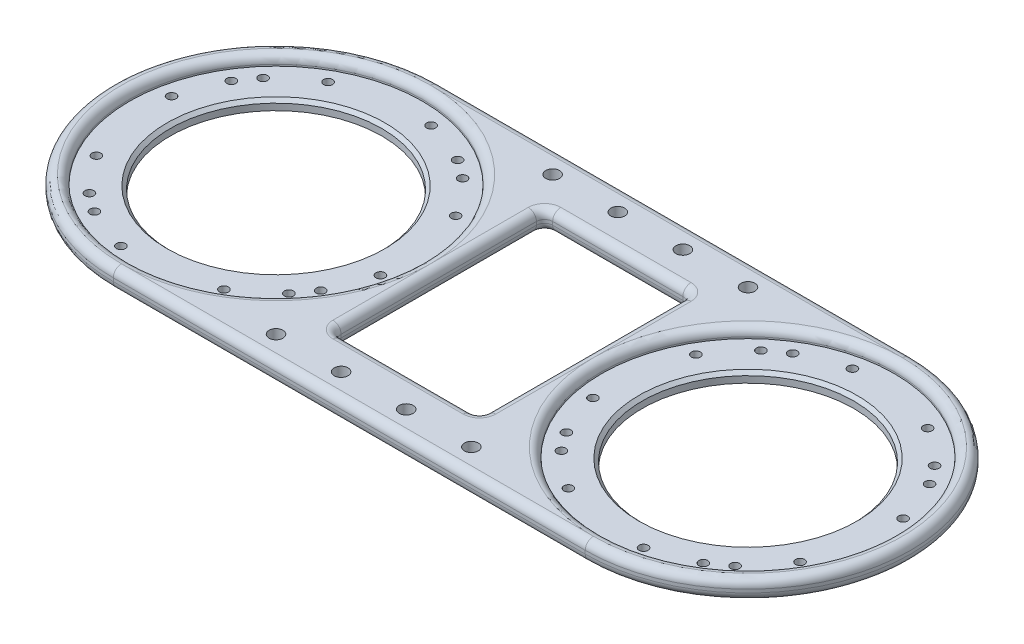
SolidWorks part; units mm, degrees
ref_plane "前视基准面" through (0, 0, 0) normal (0, 0, 1) x (1, 0, 0)
ref_plane "上视基准面" through (0, 0, 0) normal (0, 1, 0) x (1, 0, 0)
ref_plane "右视基准面" through (0, 0, 0) normal (1, 0, 0) x (0, 0, -1)
other "Configuration Table"
sketch "草图1" plane through (0, 0, 0) normal (0, 1, 0) x (1, 0, 0)
  line L0 (-145, 0) -> (145, 0) construction
  line L1 (-145, 100) -> (145, 100)
  line L2 (-145, -100) -> (145, -100)
  arc A0 (-145, 100) -> (-145, -100) centre (-145, 0) ccw
  arc A1 (145, -100) -> (145, 100) centre (145, 0) ccw
  point P3 (0, 0)
  dimension "D1" = 100
  dimension "D2" = 290
extrude "凸台-拉伸1" add sketch "草图1" along normal blind 6 and the other way blind 6
sketch "草图2" plane through (0, 0, 0) normal (0, 0, 1) x (1, 0, 0)
  line L0 (-145, 6) -> (-145, -6) construction
  line L1 (-145, -6) -> (-80, -6)
  line L2 (-145, -6) -> (145, -6) construction
  line L3 (-80, -6) -> (-80, 0)
  line L4 (-80, 0) -> (-55, 0)
  line L5 (-55, 0) -> (-55, 6)
  line L6 (-145, 6) -> (145, 6) construction
  line L7 (-55, 6) -> (-145, 6)
  line L8 (-145, 6) -> (-145, -6)
  dimension "D1" = 130
  dimension "D2" = 180
revolve "切除-旋转1" cut sketch "草图2" angle 360 about L0
sketch "草图3" plane through (0, 0, 0) normal (0, 1, 0) x (1, 0, 0)
  line L0 (-145, 0) -> (-129.4354, 79.7452) construction
  line L1 (-73.8216, 39.1816) -> (-145, 0) construction
  line L2 (-102.9484, 69.5214) -> (-145, 0) construction
  line L3 (-91.648, 61.2791) -> (-145, 0) construction
  line L4 (-145, 0) -> (-145, 81.25) construction
  circle A0 centre (-145, 0) radius 81.25 construction
  circle A1 centre (-102.9484, 69.5214) radius 2.75
  circle A2 centre (-91.648, 61.2791) radius 2.75
  circle A3 centre (-73.8216, 39.1816) radius 2.75
  circle A4 centre (-129.4354, 79.7452) radius 2.75
  circle A5 centre (-145, 0) radius 65 construction
  circle A18 centre (-75.4786, -42.0516) radius 2.75
  circle A19 centre (-83.7209, -53.352) radius 2.75
  circle A20 centre (-105.8184, -71.1784) radius 2.75
  circle A21 centre (-65.2548, -15.5646) radius 2.75
  circle A22 centre (-187.0516, -69.5214) radius 2.75
  circle A23 centre (-198.352, -61.2791) radius 2.75
  circle A24 centre (-216.1784, -39.1816) radius 2.75
  circle A25 centre (-160.5646, -79.7452) radius 2.75
  circle A26 centre (-214.5214, 42.0516) radius 2.75
  circle A27 centre (-206.2791, 53.352) radius 2.75
  circle A28 centre (-184.1816, 71.1784) radius 2.75
  circle A29 centre (-224.7452, 15.5646) radius 2.75
  point P41 (-145, 0)
  dimension "D1" = 162.5
  dimension "D2" = 5.5
  dimension "D3" = 50.124
  dimension "D4" = 20.124
  dimension "D5" = 20.124
  dimension "D6" = 11.044
  dimension "D7" = 4
extrude "切除-拉伸1" cut sketch "草图3" against normal up to next
mirror "镜向1" about plane through (0, 0, 0) normal (1, 0, 0) of "切除-拉伸1", "切除-旋转1"
sketch "草图4" plane through (0, 6, 0) normal (0, 1, 0) x (1, 0, 0)
  line L0 (0, -80) -> (0, -100) construction
  line L1 (-145, -100) -> (145, -100) construction
  line L2 (-64, -100) -> (64, -100)
  arc A0 (0, -80) -> (64, -100) centre (64, 12.4) ccw
  arc A1 (0, -80) -> (-64, -100) centre (-64, 12.4) cw
  dimension "D1" = 20
  dimension "D2" = 64
extrude "切除-拉伸2" [suppressed] cut sketch "草图4" against normal up to next
fillet "圆角1" radius 5 4 edges at (0, -6, -100) (245, -6, 0) (0, -6, 100) (-245, -6, 0)
fillet "圆角2" radius 5 6 edges at (0, 6, -100) (245, 6, 0) (0, 6, 100) (-245, 6, 0) (-145, 6, 90) (145, 6, 90)
chamfer "倒角1" distance 2 angle 45 2 edges at (-145, 0, 65) (145, 0, 65)
sketch "草图5" [suppressed] plane through (0, 0, 0) normal (0, 0, 1) x (1, 0, 0)
  line L0 (-40, 6) -> (40, 6)
  line L1 (64, 6) -> (0, 6) construction
  line L2 (40, 6) -> (25, 86)
  line L3 (25, 86) -> (-25, 86)
  line L4 (0, 86) -> (0, 6) construction
  line L5 (-40, 6) -> (-25, 86)
  dimension "D1" = 80
  dimension "D2" = 50
  dimension "D3" = 80
extrude "凸台-拉伸2" [suppressed] add sketch "草图5" along normal mid plane 90
sketch "草图6" [suppressed] plane through (0, 0, 0) normal (1, 0, 0) x (0, 0, -1)
  line L0 (0, 86) -> (0, 6) construction
  line L1 (-45, 6) -> (45, 6) construction
  line L8 (-45, 86) -> (45, 86) construction
  line L16 (45, 6) -> (45, 86) construction
  line L17 (-39, 6) -> (39, 6)
  line L18 (-39, 6) -> (-39, 86)
  line L19 (-39, 86) -> (39, 86)
  line L20 (39, 6) -> (39, 86)
  line L21 (-39, 6) -> (39, 86) construction
  line L22 (-39, 86) -> (39, 6) construction
  point P5 (0, 6)
  point P6 (0, 46)
  dimension "D1" = 6
extrude "切除-拉伸3" [suppressed] cut sketch "草图6" against normal mid plane 150
sketch "草图7" [suppressed] plane through (0, 0, 0) normal (1, 0, 0) x (0, 0, -1)
  line L0 (-45, 6) -> (45, 6) construction
  line L1 (-45, 6) -> (45, 6) construction
  line L2 (45, 6) -> (95, 6) construction
  line L3 (70, 6) -> (45, 46)
  line L4 (45, 6) -> (45, 86) construction
rib "筋2" [suppressed] sketch "草图7" sketch "草图7" thickness 5 extrusion direction parallel to sketch draft on no parameters "D1"=5
sketch "草图8" [suppressed] plane through (0, 0, 0) normal (1, 0, 0) x (0, 0, -1)
  line L0 (-73.8482, 6) -> (-45, 6) construction
  line L1 (-73.8482, 6) -> (-45, 46)
  line L2 (-45, 6) -> (-45, 86) construction
rib "筋3" [suppressed] sketch "草图8" sketch "草图8" thickness 5 extrusion direction parallel to sketch draft on no parameters "D1"=5
sketch "草图9" [suppressed] plane through (0, 0, 45) normal (0, 0, 1) x (1, 0, 0)
  line L0 (25, 86) -> (-25, 86) construction
  line L1 (-17.5, 78) -> (17.5, 78) construction
  line L2 (-17.5, 78) -> (-17.5, 28) construction
  line L3 (-17.5, 28) -> (17.5, 28) construction
  line L4 (17.5, 78) -> (17.5, 28) construction
  line L5 (0, 86) -> (0, 6) construction
  circle A0 centre (-17.5, 78) radius 4.3
  circle A1 centre (17.5, 78) radius 4.3
  circle A2 centre (17.5, 28) radius 4.3
  circle A3 centre (-17.5, 28) radius 4.3
  point P9 (0, 78)
  dimension "D2" = 8.6
  dimension "D1" = 8
  dimension "D3" = 35
  dimension "D4" = 50
extrude "切除-拉伸4" [suppressed] cut sketch "草图9" against normal up to surface (90 mm away) up to face at (0, 0, -100)
fillet "圆角4" [suppressed] radius 8
fillet "圆角5" [suppressed] radius 6
fillet "圆角6" [suppressed] radius 6
sketch "草图10" [suppressed] plane through (0, 6, 0) normal (0, 1, 0) x (1, 0, 0)
  line L0 (-45.08, 25) -> (45.08, 25)
  line L1 (46.6394, 31) -> (-46.6394, 31) construction
  line L2 (45.08, -25) -> (-45.08, -25)
  line L3 (-42, 0) -> (42, 0) construction
  arc A0 (45.08, 25) -> (45.08, -25) centre (145, 0) ccw
  arc A1 (-45.08, -25) -> (-45.08, 25) centre (-145, 0) ccw
  circle A2 centre (145, 0) radius 95 construction
  dimension "D1" = 8
  dimension "D2" = 6
extrude "切除-拉伸5" [suppressed] cut sketch "草图10" against normal up to next
fillet "圆角7" [suppressed] radius 5
sketch "草图11" plane through (0, 6, 0) normal (0, 1, 0) x (1, 0, 0)
  line L0 (-275.0843, 0) -> (287.0305, 0) construction
  line L1 (0, 0) -> (0, 187.1026) construction
  line L2 (-45, 65) -> (45, 65)
  line L3 (-45, 65) -> (-45, -65)
  line L4 (-45, -65) -> (45, -65)
  line L5 (45, 65) -> (45, -65)
  dimension "D1" = 90
  dimension "D2" = 130
extrude "切除-拉伸6" cut sketch "草图11" against normal blind 47
fillet "圆角8" radius 5 12 edges at (-45, -6, 0) (0, -6, 65) (0, -6, -65) (45, -6, 0) (45, 0, -65) (-45, 0, -65) (45, 0, 65) (-45, 0, 65) (0, 6, 65) (45, 6, 0) (-45, 6, 0) (0, 6, -65)
sketch "草图12" plane through (0, 6, 0) normal (0, 1, 0) x (1, 0, 0)
  line L0 (-265.7211, 0) -> (250.8692, 0) construction
  line L1 (0, 152.8784) -> (0, -181.2909) construction
  circle A1 centre (60, -85) radius 4.25
  circle A2 centre (20, -85) radius 4.25
  circle A3 centre (-20, -85) radius 4.25
  circle A4 centre (-60, -85) radius 4.25
  circle A5 centre (20, 85) radius 4.25
  circle A6 centre (60, 85) radius 4.25
  circle A7 centre (-60, 85) radius 4.25
  circle A8 centre (-20, 85) radius 4.25
  dimension "D1" = 8.5
  dimension "D2" = 85
  dimension "D3" = 20
  dimension "D4" = 40
extrude "切除-拉伸7" cut sketch "草图12" against normal blind 47
